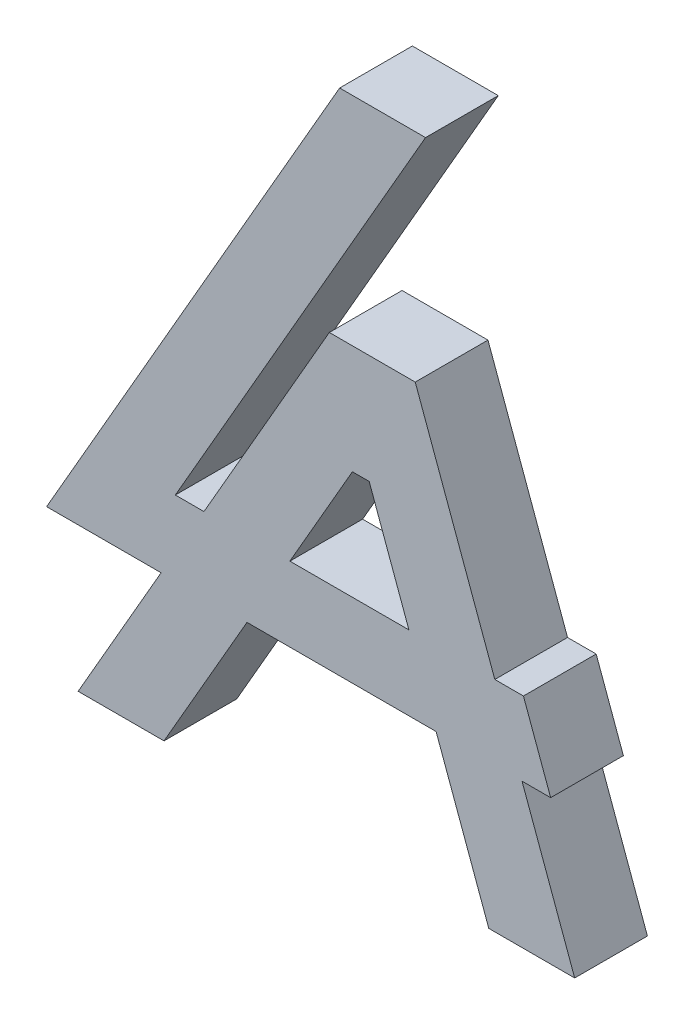
SolidWorks part; units mm, degrees
note: The reader was unsure of these and kept them because the rebuilt part matched: thickness of "Base-Flange1", "Sheet-Metal1", "Sheet-Metal2", "Sheet-Metal3".
ref_plane "Front Plane" through (0, 0, 0) normal (0, 0, 1) x (1, 0, 0)
ref_plane "Top Plane" through (0, 0, 0) normal (0, 1, 0) x (1, 0, 0)
ref_plane "Right Plane" through (0, 0, 0) normal (1, 0, 0) x (0, 0, -1)
sketch "Sketch2" plane through (0, 0, 0) normal (0, 0, 1) x (1, 0, 0)
  line L0 (0, 0) -> (7.1795, 0)
  line L1 (7.1795, 0) -> (-7.3102, -25.1715)
  line L2 (-7.3102, -25.1715) -> (7.6898, -25.1715)
  line L3 (7.6898, -25.1715) -> (22.1795, 0)
  line L4 (22.1795, 0) -> (55.2006, 0)
  line L5 (55.2006, 0) -> (64.3989, -25.1715)
  line L6 (64.3989, -25.1715) -> (79.3989, -25.1715)
  line L7 (79.3989, -25.1715) -> (70.2006, 0)
  line L8 (51.5535, 51.0285) -> (36.5535, 51.0285)
  line L9 (36.5535, 51.0285) -> (14.6628, 13)
  line L10 (14.6628, 13) -> (9.6628, 13)
  line L11 (9.6628, 13) -> (53.3539, 88.9)
  line L12 (53.3539, 88.9) -> (38.3539, 88.9)
  line L13 (38.3539, 88.9) -> (-1.9193, 18.9375)
  line L15 (70.2006, 0) -> (75.2006, 0)
  line L16 (75.2006, 0) -> (70.4501, 13)
  line L17 (70.4501, 13) -> (65.4501, 13)
  line L18 (65.4501, 13) -> (51.5535, 51.0285)
  line L19 (-1.9193, 18.9375) -> (-12.8205, 0)
  line L20 (-12.8205, 0) -> (0, 0)
  point P3 (44.0535, 51.0285)
  dimension "D1" = 76.2
  dimension "D2" = 88.9
  dimension "D3" = 15
  dimension "D4" = 13
  dimension "D5" = 13
  dimension "D6" = 50
  dimension "D7" = 13
  dimension "D8" = 5
  dimension "D9" = 5
base flange "Base-Flange1" sketch "Sketch2" thickness 12.7 reverse thickness direction no parameters "D1"=1
sketch "Sketch12" plane through (0, 0, 0) normal (0, 0, 1) x (1, 0, 0)
  line L0 (29.6628, 13) -> (50.4501, 13)
  line L1 (50.4501, 13) -> (43.5147, 31.9789)
  line L2 (43.5147, 31.9789) -> (40.5878, 31.9789)
  line L3 (40.5878, 31.9789) -> (29.6628, 13)
  line L4 (7.6898, -25.1715) -> (22.1795, 0) construction
  line L5 (55.2006, 0) -> (64.3989, -25.1715) construction
  line L8 (14.6628, 13) -> (9.6628, 13) construction
extrude "Cut-Extrude1" cut sketch "Sketch12" against normal through all normal cut yes
scale "Scale1" scale about origin uniform scaling yes scale factor 0.55
sketch "Sketch13" plane through (0, 0, 0) normal (0, 0, 1) x (1, 0, 0)
  line L1 (22.0311, 7.15) -> (22.3233, 17.5884) construction
  line L2 (16.3145, 7.15) -> (27.7476, 7.15) construction
  circle A0 centre (22.1772, 12.3692) radius 12.7 construction
  circle A1 centre (22.1772, 12.3692) radius 38.1
  point P6 (22.1772, 12.3692)
  dimension "D1" = 25.4
sketch "Bend-Lines1" [suppressed] plane through (0, 0, 0) normal (0, 1, 0) x (1, 0, 0)
sketch "Bounding-Box1" [suppressed] plane through (0, 0, 0) normal (0, 1, 0) x (1, 0, 0)
sheet metal parameters "Sheet-Metal1" thickness 12.7 parameters "D1"=1
flat pattern "Flat-Pattern1" [suppressed]
sketch "Bend-Lines2" plane through (0, 0, 0) normal (0, 1, 0) x (1, 0, 0)
sketch3d "Bounding-Box2" [suppressed]
  line L0 (54.9445, 92.5319, 0) -> (80.6509, -24.8974, 0) construction
  line L1 (-29.0514, 74.1443, 0) -> (-3.345, -43.285, 0) construction
  line L2 (54.9445, 92.5319, 0) -> (-29.0514, 74.1443, 0) construction
  line L3 (80.6509, -24.8974, 0) -> (-3.345, -43.285, 0) construction
sheet metal parameters "Sheet-Metal2" thickness 12.7 parameters "D1"=1, "D7"=3
flat pattern "Flat-Pattern1"
sketch "Bend-Lines2" plane through (0, 0, 0) normal (0, 1, 0) x (1, 0, 0)
sketch3d "Bounding-Box2" [suppressed]
  line L0 (54.9445, 92.5319, 0) -> (80.6509, -24.8974, 0) construction
  line L1 (-29.0514, 74.1443, 0) -> (-3.345, -43.285, 0) construction
  line L2 (54.9445, 92.5319, 0) -> (-29.0514, 74.1443, 0) construction
  line L3 (80.6509, -24.8974, 0) -> (-3.345, -43.285, 0) construction
sheet metal parameters "Sheet-Metal3" thickness 12.7 parameters "D1"=1, "D7"=3
flat pattern "Flat-Pattern1"
sketch "Bend-Lines2" plane through (0, 0, 0) normal (0, 1, 0) x (1, 0, 0)
sketch3d "Bounding-Box2" [suppressed]
  line L0 (54.9445, 92.5319, 0) -> (80.6509, -24.8974, 0) construction
  line L1 (-29.0514, 74.1443, 0) -> (-3.345, -43.285, 0) construction
  line L2 (54.9445, 92.5319, 0) -> (-29.0514, 74.1443, 0) construction
  line L3 (80.6509, -24.8974, 0) -> (-3.345, -43.285, 0) construction
